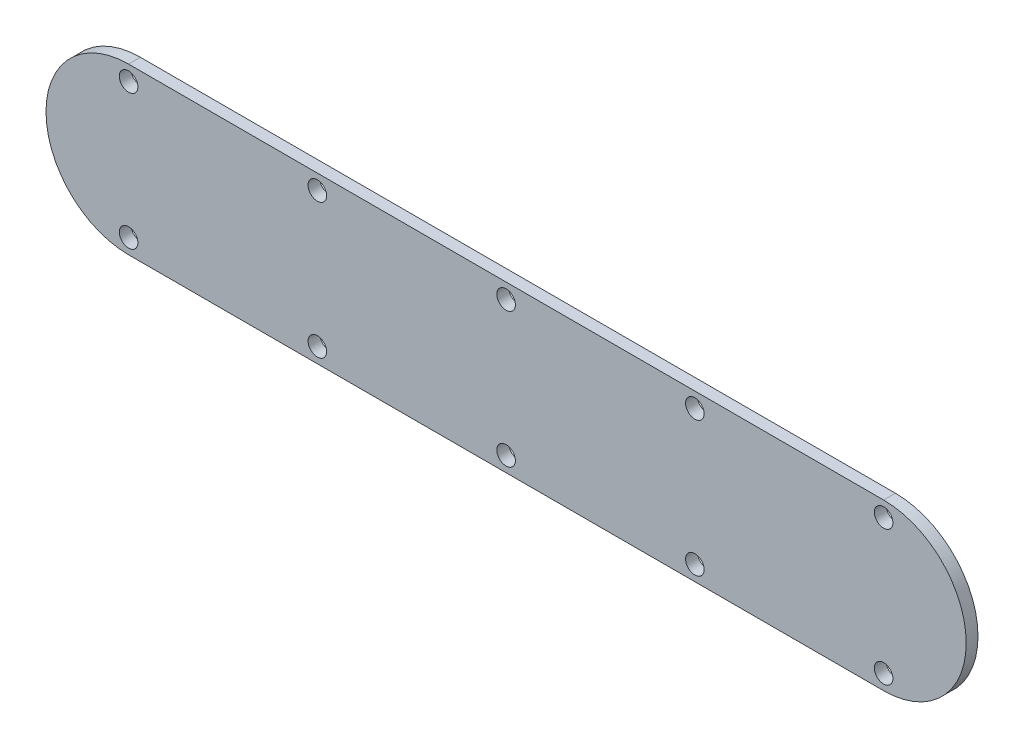
SolidWorks part; units mm, degrees
material "6061 Alloy"
ref_plane "Front" through (0, 0, 0) normal (0, 0, 1) x (1, 0, 0)
ref_plane "Top" through (0, 0, 0) normal (0, 1, 0) x (1, 0, 0)
ref_plane "Right" through (0, 0, 0) normal (1, 0, 0) x (0, 0, -1)
sketch "Sketch1" plane through (0, 0, 0) normal (0, 0, 1) x (1, 0, 0)
  line L1 (123.825, 22.225) -> (-123.825, 22.225)
  line L2 (123.825, 22.225) -> (123.825, -22.225)
  line L3 (123.825, -22.225) -> (-123.825, -22.225)
  line L4 (-123.825, 22.225) -> (-123.825, -22.225)
  line L5 (123.825, 22.225) -> (-123.825, -22.225) construction
  line L6 (123.825, -22.225) -> (-123.825, 22.225) construction
  point P0 (0, 0)
  dimension "D1" = 247.65
  dimension "D2" = 44.45
extrude "Boss-Extrude1" add sketch "Sketch1" along normal blind 3.175
sketch "Sketch2" plane through (0, 0, 3.175) normal (0, 0, 1) x (1, 0, 0)
  line L0 (101.6, 0) -> (-101.6, 0) construction
  line L1 (101.6, -14.351) -> (-101.6, -14.351)
  line L2 (101.6, 14.351) -> (-101.6, 14.351)
  line L3 (101.6, -22.225) -> (-101.6, -22.225)
  line L4 (101.6, 22.225) -> (-101.6, 22.225)
  arc A0 (101.6, -14.351) -> (101.6, 14.351) centre (101.6, 0) ccw
  arc A1 (-101.6, 14.351) -> (-101.6, -14.351) centre (-101.6, 0) ccw
  arc A2 (-101.6, 22.225) -> (-101.6, -22.225) centre (-101.6, 0) ccw
  arc A3 (101.6, -22.225) -> (101.6, 22.225) centre (101.6, 0) ccw
  point P2 (0, 0)
  line M9 (-123.825, 22.225) -> (-123.825, -22.225)
  line M10 (-123.825, -22.225) -> (123.825, -22.225)
  line M11 (123.825, -22.225) -> (123.825, 22.225)
  line M12 (123.825, 22.225) -> (-123.825, 22.225)
  dimension "D1" = 203.2
  dimension "D2" = 28.702
  dimension "D3" = 7.874
extrude "Cut-Extrude1" cut sketch "Sketch2" against normal through all contours A2 M12 M9 | A2 M9 M10 | A3 M10 M11 | A3 M11 M12 region at (118.8606, -17.2606, 3.175) region at (-118.8606, -17.2606, 3.175) region at (118.8606, 17.2606, 3.175) region at (-118.8606, 17.2606, 3.175)
sketch "Sketch3" plane through (0, 0, 3.175) normal (0, 0, 1) x (1, 0, 0)
  line L2 (101.6, 18.161) -> (-101.6, 18.161)
  line L3 (101.6, 18.161) -> (-101.6, 18.161) construction
  line L4 (-101.6, 18.161) -> (0, 18.161) construction
  line L5 (-101.6, -18.161) -> (101.6, -18.161)
  line L6 (-101.6, -18.161) -> (101.6, -18.161) construction
  line L7 (0, 18.161) -> (101.6, 18.161) construction
  line L8 (-101.6, -18.161) -> (0, -18.161) construction
  line L9 (0, -18.161) -> (101.6, -18.161) construction
  point P0 (0, 18.161)
  point P1 (-101.6, 18.161)
  point P6 (0, -18.161)
  point P7 (101.6, 18.161)
  point P8 (101.6, -18.161)
  point P9 (-50.8, 18.161)
  point P10 (-101.6, -18.161)
  point P13 (50.8, 18.161)
  point P14 (-50.8, -18.161)
  point P15 (50.8, -18.161)
  dimension "D1" = 4.064
  dimension "D2" = 4.064
hole_wizard "#10 (0.1935) Diameter Hole1" positions "Sketch6" profile "Sketch7" hole size "#10" standard "ANSI Inch" end condition through all
sketch "Sketch6" plane through (0, 0, 3.175) normal (0, 0, 1) x (1, 0, 0)
  point P0 (-101.6, 18.161)
  point P3 (-50.8, 18.161)
  point P6 (0, 18.161)
  point P9 (50.8, 18.161)
  point P12 (101.6, 18.161)
  point P15 (101.6, -18.161)
  point P18 (50.8, -18.161)
  point P21 (0, -18.161)
  point P24 (-50.8, -18.161)
  point P27 (-101.6, -18.161)
sketch "Sketch7" plane through (-101.6, 18.161, 3.175) normal (1, 0, 0) x (0, -1, 0)
  line L0 (0, 0) -> (0, 3.175)
  line L1 (0, 3.175) -> (2.5, 3.175)
  line L2 (2.5, 3.175) -> (2.5, 0)
  line L5 (2.5, 0) -> (0, 0)
  line L11 (0, -6.35) -> (0, 107.95) construction
  dimension "Thru Hole Dia." = 5
  dimension "Thru Hole Depth" = 3.175
